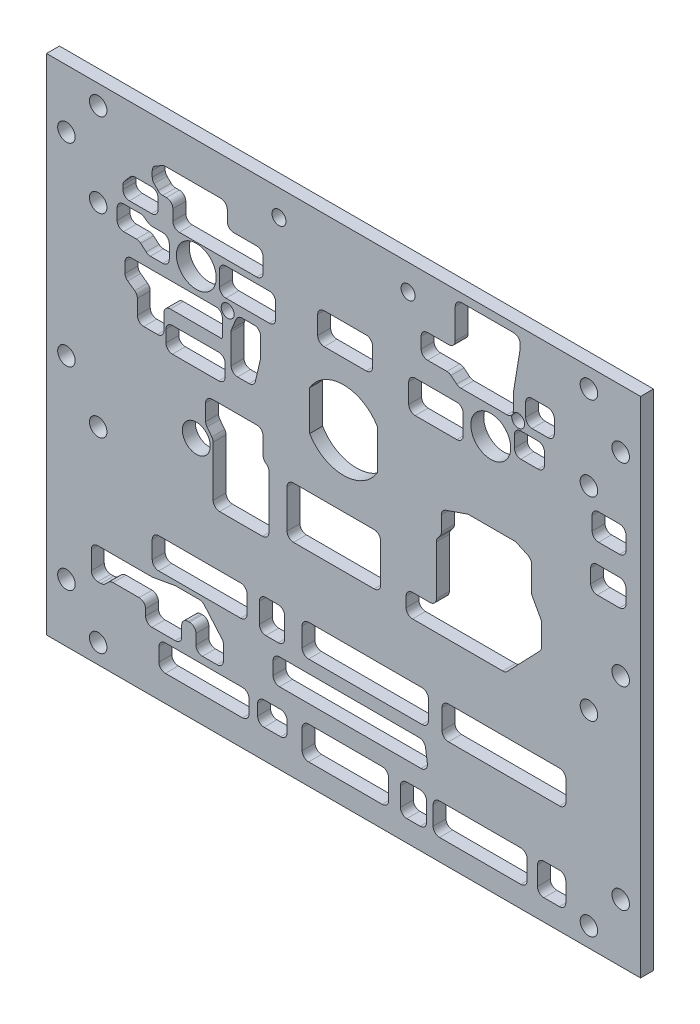
SolidWorks part; units mm, degrees
ref_plane "Front Plane" through (0, 0, 0) normal (0, 0, 1) x (1, 0, 0)
ref_plane "Top Plane" through (0, 0, 0) normal (0, 1, 0) x (1, 0, 0)
ref_plane "Right Plane" through (0, 0, 0) normal (1, 0, 0) x (0, 0, -1)
sketch "Sketch1" plane through (0, 0, 0) normal (0, 0, 1) x (1, 0, 0)
  line L8 (0, 123.825) -> (-146.05, 123.825)
  line L9 (-146.05, 123.825) -> (-146.05, 0)
  line L10 (-146.05, 0) -> (0, 0)
  line L11 (0, 0) -> (0, 123.825)
extrude "Boss-Extrude1" add sketch "Sketch1" against normal blind 3.175
hole_wizard "#6 Clearance Hole1" positions "Sketch3" profile "Sketch2" hole size "#6" standard "ANSI Inch" end condition through all
sketch "Sketch3" plane through (0, 0, -3.175) normal (0, 0, -1) x (-1, 0, 0)
  line L0 (88.9, 117.475) -> (57.15, 117.475) construction
  point P0 (12.7, 119.0625)
  point P9 (133.35, 119.0625)
  point P12 (141.1605, 109.5375)
  point P15 (133.35, 98.425)
  point P18 (141.1605, 61.9125)
  point P21 (133.35, 50.673)
  point P24 (133.35, 4.7625)
  point P27 (12.7, 4.7625)
  point P30 (12.7, 50.673)
  point P33 (12.7, 98.425)
  point P36 (4.8895, 109.5375)
  point P39 (141.1605, 14.2875)
  point P42 (4.8895, 14.2875)
  point P45 (4.8895, 61.9125)
sketch "Sketch2" plane through (-12.7, 119.0625, -3.175) normal (1, 0, 0) x (0, 1, 0)
  line L0 (0, 0) -> (0, 3.175)
  line L1 (0, 3.175) -> (2.1526, 3.175)
  line L2 (2.1526, 3.175) -> (2.1526, 0)
  line L5 (2.1526, 0) -> (0, 0)
  line L11 (0, -6.35) -> (0, 107.95) construction
  dimension "Thru Hole Dia." = 4.3053
  dimension "Thru Hole Depth" = 3.175
sketch "Sketch4" plane through (0, 0, -3.175) normal (0, 0, -1) x (-1, 0, 0)
  line L0 (109.22, 96.901) -> (89.8757, 96.901) construction
  line L1 (109.22, 96.901) -> (101.5141, 91.3023) construction
  line L2 (81.3435, 85.0323) -> (81.3435, 75.2417)
  line L3 (64.7065, 75.2417) -> (64.7065, 85.0323)
  line L5 (36.83, 96.901) -> (21.0814, 96.901) construction
  line L6 (36.83, 96.901) -> (30.0948, 103.6362) construction
  circle A0 centre (36.83, 96.901) radius 4.9022
  circle A1 centre (36.83, 60.325) radius 3.7703
  circle A2 centre (109.22, 60.325) radius 3.429
  circle A3 centre (109.22, 96.901) radius 4.9022
  circle A4 centre (36.83, 66.525) radius 1.125
  circle A5 centre (101.5141, 91.3023) radius 1.5875
  arc A6 (81.3435, 85.0323) -> (64.7065, 85.0323) centre (73.025, 80.137) ccw
  arc A7 (64.7065, 75.2417) -> (81.3435, 75.2417) centre (73.025, 80.137) ccw
  circle A8 centre (30.0948, 103.6362) radius 1.5875
  dimension "D1" = 7.5406
  dimension "D2" = 9.8044
  dimension "D3" = 6.858
  dimension "D4" = 2.25
  dimension "D5" = 3.175
  dimension "D7" = 9.8044
  dimension "D9" = 315
  dimension "D11" = 3.175
  dimension "D6" = 9.525
  dimension "D8" = 36
  dimension "D10" = 9.525
  dimension "D12" = 6.2
extrude "Switch Mount Holes" cut sketch "Sketch4" against normal through all
hole_wizard "#4 Clearance Hole1" positions "Sketch6" profile "Sketch5" hole size "#4" standard "ANSI Inch" end condition through all
sketch "Sketch6" plane through (0, 0, 0) normal (0, 0, 1) x (1, 0, 0)
  point P3 (-88.9, 117.475)
  point P6 (-57.15, 117.475)
sketch "Sketch5" plane through (-88.9, 117.475, 0) normal (1, 0, 0) x (0, -1, 0)
  line L0 (0, 0) -> (0, 3.175)
  line L1 (0, 3.175) -> (1.7272, 3.175)
  line L2 (1.7272, 3.175) -> (1.7272, 0)
  line L5 (1.7272, 0) -> (0, 0)
  line L11 (0, -6.35) -> (0, 107.95) construction
  dimension "Thru Hole Dia." = 3.4544
  dimension "Thru Hole Depth" = 3.175
sketch "Sketch7" plane through (0, 0, -3.175) normal (0, 0, -1) x (-1, 0, 0)
  line L0 (50.1883, 55.6576) -> (50.1883, 67.7772)
  line L9 (30.4526, 77.4046) -> (27.7399, 76.1861)
  line L10 (26.8029, 74.738) -> (26.8029, 68.7138)
  line L16 (48.9573, 70.478) -> (48.9573, 74.1496)
  line L17 (47.8891, 75.6498) -> (42.6693, 77.4567)
  line L18 (42.15, 77.544) -> (31.1031, 77.544)
  line L22 (24.3417, 58.3195) -> (24.3417, 63.425)
  line L24 (5.1812, 94.0944) -> (10.326, 94.0944)
  line L25 (3.5937, 92.5069) -> (3.5937, 89.2086)
  line L26 (5.1812, 87.6211) -> (10.326, 87.6211)
  line L27 (11.9135, 92.5069) -> (11.9135, 89.2086)
  line L28 (5.1812, 82.7314) -> (10.6748, 82.7314)
  line L29 (3.5937, 81.1439) -> (3.5937, 77.808)
  line L30 (5.1812, 76.2205) -> (10.6748, 76.2205)
  line L31 (12.2623, 81.1439) -> (12.2623, 77.808)
  line L36 (65.5088, 62.7223) -> (85.3289, 62.7223)
  line L37 (63.9213, 61.1348) -> (63.9213, 51.6801)
  line L38 (65.5088, 50.0926) -> (85.3289, 50.0926)
  line L39 (86.9164, 61.1348) -> (86.9164, 51.6801)
  line L40 (45.5644, 120.203) -> (45.5644, 112.8447)
  line L41 (47.1519, 111.2572) -> (52.3642, 111.2572)
  line L42 (53.9517, 109.6697) -> (53.9517, 106.9355)
  line L43 (52.3642, 105.348) -> (47.5969, 105.348)
  line L44 (46.598, 104.9944) -> (45.1842, 103.8499)
  line L45 (44.1854, 103.4962) -> (32.8826, 103.4962)
  line L49 (22.7874, 110.0698) -> (26.67, 110.0698)
  line L50 (28.2575, 108.4823) -> (28.2575, 105.2469)
  line L51 (26.67, 103.6594) -> (22.7874, 103.6594)
  line L52 (21.1999, 105.2469) -> (21.1999, 108.4823)
  line L53 (31.0254, 97.333) -> (31.0254, 100.1621)
  line L54 (29.4379, 101.7496) -> (25.2171, 101.7496)
  line L55 (23.6296, 100.1621) -> (23.6296, 97.333)
  line L56 (25.2171, 95.7455) -> (29.4379, 95.7455)
  line L57 (45.1936, 100.0129) -> (55.4124, 100.0129)
  line L58 (56.9999, 98.4254) -> (56.9999, 93.6299)
  line L59 (55.4124, 92.0424) -> (45.1936, 92.0424)
  line L60 (43.6061, 93.6299) -> (43.6061, 98.4254)
  line L61 (67.4661, 103.1819) -> (77.7971, 103.1819)
  line L62 (79.3846, 101.5944) -> (79.3846, 97.1115)
  line L63 (77.7971, 95.524) -> (67.4661, 95.524)
  line L64 (65.8786, 97.1115) -> (65.8786, 101.5944)
  line L65 (101.6113, 112.8205) -> (101.6113, 110.2692)
  line L66 (100.0238, 108.6817) -> (94.374, 108.6817)
  line L67 (92.7865, 107.0942) -> (92.7865, 103.6594)
  line L68 (94.374, 102.0719) -> (113.3987, 102.0719)
  line L69 (114.9862, 103.6594) -> (114.9862, 106.2952)
  line L70 (116.5737, 107.8827) -> (117.4821, 107.8827)
  line L71 (118.6047, 108.3477) -> (119.594, 109.337)
  line L72 (120.059, 110.4596) -> (120.059, 111.8874)
  line L73 (119.235, 113.2792) -> (117.5341, 114.2123)
  line L74 (116.7706, 114.408) -> (103.1988, 114.408)
  line L75 (118.6106, 106.776) -> (118.6106, 104.2323)
  line L76 (120.1981, 102.6448) -> (125.6772, 102.6448)
  line L77 (127.2647, 104.2323) -> (127.2647, 105.1854)
  line L78 (126.8771, 106.2249) -> (125.4846, 107.8322)
  line L79 (124.2782, 108.3802) -> (120.1916, 108.3635)
  line L80 (128.6873, 99.6767) -> (128.6873, 96.9557)
  line L81 (127.0998, 95.3682) -> (123.9282, 95.3682)
  line L82 (122.8887, 94.9806) -> (121.5452, 93.8167)
  line L83 (120.5057, 93.429) -> (117.4622, 93.429)
  line L84 (115.8747, 95.0165) -> (115.8747, 98.3811)
  line L85 (117.4622, 99.9686) -> (120.0973, 99.9686)
  line L86 (120.9827, 100.2384) -> (122.1076, 100.9943)
  line L87 (122.993, 101.2642) -> (127.0998, 101.2642)
  line L88 (91.2932, 100.6292) -> (101.9492, 100.6292)
  line L89 (103.5367, 99.0417) -> (103.5367, 95.3671)
  line L90 (101.9492, 93.7796) -> (91.2932, 93.7796)
  line L91 (89.7057, 95.3671) -> (89.7057, 99.0417)
  line L92 (93.3875, 89.9303) -> (93.3875, 85.5072)
  line L93 (93.4289, 85.1472) -> (94.7051, 79.6669)
  line L94 (96.2512, 78.4394) -> (99.0869, 78.4394)
  line L95 (100.6744, 80.0269) -> (100.6744, 87.2579)
  line L96 (100.552, 87.8693) -> (99.4367, 90.5417)
  line L97 (97.9716, 91.5178) -> (94.975, 91.5178)
  line L98 (116.6884, 76.8675) -> (116.6884, 79.8001)
  line L99 (115.1009, 81.3876) -> (103.7165, 81.3876)
  line L100 (102.129, 79.8001) -> (102.129, 76.8675)
  line L101 (103.7165, 75.28) -> (115.1009, 75.28)
  line L102 (118.7649, 77.6401) -> (122.1358, 77.6401)
  line L107 (125.1538, 90.7081) -> (104.3937, 90.7081)
  line L108 (102.8062, 89.1206) -> (102.8062, 85.2592)
  line L110 (92.7865, 68.98) -> (92.7865, 64.8285)
  line L111 (92.0912, 63.5154) -> (92.0685, 63.5)
  line L112 (91.3732, 62.1869) -> (91.3732, 49.1513)
  line L113 (92.9607, 47.5638) -> (103.499, 47.5638)
  line L114 (105.0865, 49.1513) -> (105.0865, 61.5326)
  line L115 (105.4181, 62.5037) -> (106.6032, 64.0363)
  line L116 (106.9348, 65.0074) -> (106.9348, 68.98)
  line L117 (105.3473, 70.5675) -> (94.374, 70.5675)
  line L118 (19.9317, 34.7214) -> (47.2287, 34.7214)
  line L119 (48.8162, 33.1339) -> (48.8162, 28.2593)
  line L120 (47.2287, 26.6718) -> (19.9317, 26.6718)
  line L121 (18.3442, 28.2593) -> (18.3442, 33.1339)
  line L122 (52.1537, 33.3607) -> (52.1537, 28.7019)
  line L123 (53.7412, 27.1144) -> (81.6222, 27.1144)
  line L124 (83.2097, 28.7019) -> (83.2097, 33.3607)
  line L125 (81.6222, 34.9482) -> (53.7412, 34.9482)
  line L126 (89.0857, 34.9482) -> (92.1336, 34.9482)
  line L127 (93.7211, 33.3607) -> (93.7211, 28.4272)
  line L128 (92.1336, 26.8397) -> (89.0857, 26.8397)
  line L129 (87.4982, 28.4272) -> (87.4982, 33.3607)
  line L130 (98.3248, 34.9482) -> (118.4715, 34.9482)
  line L131 (120.059, 33.3607) -> (120.059, 29.0335)
  line L132 (96.7373, 33.3607) -> (96.7373, 29.0335)
  line L133 (98.3248, 27.446) -> (118.4715, 27.446)
  line L137 (130.8099, 18.8799) -> (131.5742, 18.1156)
  line L138 (132.6968, 17.6506) -> (133.4449, 17.6506)
  line L139 (135.0324, 19.2381) -> (135.0324, 23.7437)
  line L141 (120.198, 25.3312) -> (133.4449, 25.3312)
  line L142 (107.2606, 25.7828) -> (102.9308, 20.7547)
  line L143 (102.5462, 19.7188) -> (102.5462, 16.2301)
  line L144 (104.1337, 14.6426) -> (107.7174, 14.6426)
  line L145 (109.3049, 16.2301) -> (109.3049, 18.7206)
  line L146 (110.8924, 20.3081) -> (111.2259, 20.3081)
  line L147 (112.8134, 18.7206) -> (112.8134, 16.2076)
  line L148 (114.4009, 14.6201) -> (120.1137, 14.6201)
  line L149 (108.4635, 26.3345) -> (114.2367, 26.3345)
  line L150 (114.5127, 26.3103) -> (119.9221, 25.3554)
  line L151 (129.6874, 19.3449) -> (123.2887, 19.3449)
  line L152 (121.7012, 17.7574) -> (121.7012, 16.2076)
  line L153 (54.4377, 23.9876) -> (88.7667, 23.9876)
  line L154 (90.3542, 22.4001) -> (90.3542, 19.2172)
  line L155 (88.7667, 17.6297) -> (53.9837, 17.6297)
  line L156 (52.4121, 19.4414) -> (52.8661, 22.6242)
  line L157 (19.972, 12.9834) -> (23.773, 12.9834)
  line L158 (25.3605, 11.3959) -> (25.3605, 6.8041)
  line L159 (23.773, 5.2166) -> (19.972, 5.2166)
  line L160 (18.3845, 6.8041) -> (18.3845, 11.3959)
  line L161 (29.4607, 12.9834) -> (49.418, 12.9834)
  line L162 (51.0055, 11.3959) -> (51.0055, 6.8041)
  line L163 (49.418, 5.2166) -> (29.4607, 5.2166)
  line L164 (27.8732, 6.8041) -> (27.8732, 11.3959)
  line L165 (54.1946, 12.9834) -> (57.4655, 12.9834)
  line L166 (59.053, 11.3959) -> (59.053, 6.8041)
  line L167 (57.4655, 5.2166) -> (54.1946, 5.2166)
  line L168 (52.6071, 6.8041) -> (52.6071, 11.3959)
  line L169 (63.5238, 13.2586) -> (81.6126, 13.2586)
  line L170 (83.2001, 11.6711) -> (83.2001, 6.8041)
  line L171 (81.6126, 5.2166) -> (63.5238, 5.2166)
  line L172 (61.9363, 6.8041) -> (61.9363, 11.6711)
  line L173 (26.6062, 67.9484) -> (24.5383, 64.1904)
  line L174 (88.4887, 12.9381) -> (92.5645, 12.9381)
  line L175 (86.9012, 11.3506) -> (86.9012, 8.7068)
  line L176 (88.4887, 7.1193) -> (92.5645, 7.1193)
  line L177 (94.152, 11.3506) -> (94.152, 8.7068)
  line L178 (97.8585, 12.9381) -> (116.8363, 12.9381)
  line L179 (96.271, 11.3506) -> (96.271, 8.0414)
  line L180 (97.8585, 6.4539) -> (116.8363, 6.4539)
  line L181 (118.4238, 11.3506) -> (118.4238, 8.0414)
  line L182 (24.7832, 57.2209) -> (32.747, 48.9138)
  line L183 (51.7758, 54.0701) -> (56.0639, 54.0701)
  line L184 (57.6514, 52.4826) -> (57.6514, 50.0124)
  line L185 (33.8929, 48.4249) -> (56.0639, 48.4249)
  line L186 (49.2742, 69.5263) -> (49.8715, 68.7289)
  line L189 (31.2951, 108.7766) -> (31.2951, 105.0837)
  line L190 (43.9769, 121.7905) -> (31.1878, 121.7905)
  line L191 (29.6003, 120.203) -> (29.6003, 119.2785)
  line L192 (29.6216, 119.0193) -> (31.2738, 109.0357)
  line L194 (123.7233, 82.8593) -> (123.7233, 79.2276)
  line L195 (117.1774, 79.2276) -> (117.1774, 83.0623)
  line L196 (115.5899, 84.6498) -> (102.9278, 84.6498)
  line L197 (124.3822, 84.1469) -> (126.0824, 85.3731)
  line L198 (126.7413, 86.6607) -> (126.7413, 89.1206)
  arc A2 (116.8363, 12.9381) -> (118.4238, 11.3506) centre (116.8363, 11.3506) cw
  arc A3 (96.271, 8.0414) -> (97.8585, 6.4539) centre (97.8585, 8.0414) ccw
  arc A4 (116.8363, 6.4539) -> (118.4238, 8.0414) centre (116.8363, 8.0414) ccw
  arc A5 (97.8585, 12.9381) -> (96.271, 11.3506) centre (97.8585, 11.3506) ccw
  arc A6 (92.5645, 12.9381) -> (94.152, 11.3506) centre (92.5645, 11.3506) cw
  arc A7 (86.9012, 8.7068) -> (88.4887, 7.1193) centre (88.4887, 8.7068) ccw
  arc A8 (92.5645, 7.1193) -> (94.152, 8.7068) centre (92.5645, 8.7068) ccw
  arc A9 (63.5238, 5.2166) -> (61.9363, 6.8041) centre (63.5238, 6.8041) cw
  arc A10 (88.4887, 12.9381) -> (86.9012, 11.3506) centre (88.4887, 11.3506) ccw
  arc A11 (83.2001, 6.8041) -> (81.6126, 5.2166) centre (81.6126, 6.8041) cw
  arc A12 (81.6126, 13.2586) -> (83.2001, 11.6711) centre (81.6126, 11.6711) cw
  arc A13 (54.1946, 5.2166) -> (52.6071, 6.8041) centre (54.1946, 6.8041) cw
  arc A14 (63.5238, 13.2586) -> (61.9363, 11.6711) centre (63.5238, 11.6711) ccw
  arc A15 (59.053, 6.8041) -> (57.4655, 5.2166) centre (57.4655, 6.8041) cw
  arc A16 (57.4655, 12.9834) -> (59.053, 11.3959) centre (57.4655, 11.3959) cw
  arc A17 (54.1946, 12.9834) -> (52.6071, 11.3959) centre (54.1946, 11.3959) ccw
  arc A18 (51.0055, 6.8041) -> (49.418, 5.2166) centre (49.418, 6.8041) cw
  arc A19 (29.4607, 5.2166) -> (27.8732, 6.8041) centre (29.4607, 6.8041) cw
  arc A20 (49.418, 12.9834) -> (51.0055, 11.3959) centre (49.418, 11.3959) cw
  arc A21 (29.4607, 12.9834) -> (27.8732, 11.3959) centre (29.4607, 11.3959) ccw
  arc A22 (19.972, 5.2166) -> (18.3845, 6.8041) centre (19.972, 6.8041) cw
  arc A23 (25.3605, 6.8041) -> (23.773, 5.2166) centre (23.773, 6.8041) cw
  arc A24 (23.773, 12.9834) -> (25.3605, 11.3959) centre (23.773, 11.3959) cw
  arc A25 (19.972, 12.9834) -> (18.3845, 11.3959) centre (19.972, 11.3959) ccw
  arc A26 (90.3542, 19.2172) -> (88.7667, 17.6297) centre (88.7667, 19.2172) cw
  arc A27 (53.9837, 17.6297) -> (52.4121, 19.4414) centre (53.9837, 19.2172) cw
  arc A28 (88.7667, 23.9876) -> (90.3542, 22.4001) centre (88.7667, 22.4001) cw
  arc A29 (123.2887, 19.3449) -> (121.7012, 17.7574) centre (123.2887, 17.7574) ccw
  arc A30 (120.1137, 14.6201) -> (121.7012, 16.2076) centre (120.1137, 16.2076) ccw
  arc A31 (112.8134, 16.2076) -> (114.4009, 14.6201) centre (114.4009, 16.2076) ccw
  arc A32 (114.2367, 26.3345) -> (114.5127, 26.3103) centre (114.2367, 24.747) cw
  arc A33 (109.3049, 18.7206) -> (110.8924, 20.3081) centre (110.8924, 18.7206) cw
  arc A34 (107.7174, 14.6426) -> (109.3049, 16.2301) centre (107.7174, 16.2301) ccw
  arc A35 (102.5462, 16.2301) -> (104.1337, 14.6426) centre (104.1337, 16.2301) ccw
  arc A36 (111.2259, 20.3081) -> (112.8134, 18.7206) centre (111.2259, 18.7206) cw
  arc A37 (102.9308, 20.7547) -> (102.5462, 19.7188) centre (104.1337, 19.7188) ccw
  arc A38 (133.4449, 17.6506) -> (135.0324, 19.2381) centre (133.4449, 19.2381) ccw
  arc A39 (131.5742, 18.1156) -> (132.6968, 17.6506) centre (132.6968, 19.2381) ccw
  arc A40 (129.6874, 19.3449) -> (130.8099, 18.8799) centre (129.6874, 17.7574) cw
  arc A41 (54.4377, 23.9876) -> (52.8661, 22.6242) centre (54.4377, 22.4001) ccw
  arc A42 (135.0324, 23.7437) -> (133.4449, 25.3312) centre (133.4449, 23.7437) ccw
  arc A43 (120.198, 25.3312) -> (119.9221, 25.3554) centre (120.198, 26.9187) cw
  arc A44 (96.7373, 29.0335) -> (98.3248, 27.446) centre (98.3248, 29.0335) ccw
  arc A45 (120.059, 29.0335) -> (118.4715, 27.446) centre (118.4715, 29.0335) cw
  arc A46 (107.2606, 25.7828) -> (108.4635, 26.3345) centre (108.4635, 24.747) cw
  arc A47 (118.4715, 34.9482) -> (120.059, 33.3607) centre (118.4715, 33.3607) cw
  arc A48 (98.3248, 34.9482) -> (96.7373, 33.3607) centre (98.3248, 33.3607) ccw
  arc A49 (89.0857, 26.8397) -> (87.4982, 28.4272) centre (89.0857, 28.4272) cw
  arc A50 (93.7211, 28.4272) -> (92.1336, 26.8397) centre (92.1336, 28.4272) cw
  arc A51 (92.1336, 34.9482) -> (93.7211, 33.3607) centre (92.1336, 33.3607) cw
  arc A52 (83.2097, 33.3607) -> (81.6222, 34.9482) centre (81.6222, 33.3607) ccw
  arc A53 (81.6222, 27.1144) -> (83.2097, 28.7019) centre (81.6222, 28.7019) ccw
  arc A54 (89.0857, 34.9482) -> (87.4982, 33.3607) centre (89.0857, 33.3607) ccw
  arc A55 (52.1537, 28.7019) -> (53.7412, 27.1144) centre (53.7412, 28.7019) ccw
  arc A56 (19.9317, 26.6718) -> (18.3442, 28.2593) centre (19.9317, 28.2593) cw
  arc A57 (48.8162, 28.2593) -> (47.2287, 26.6718) centre (47.2287, 28.2593) cw
  arc A58 (52.1537, 33.3607) -> (53.7412, 34.9482) centre (53.7412, 33.3607) cw
  arc A59 (47.2287, 34.7214) -> (48.8162, 33.1339) centre (47.2287, 33.1339) cw
  arc A60 (106.9348, 68.98) -> (105.3473, 70.5675) centre (105.3473, 68.98) ccw
  arc A61 (19.9317, 34.7214) -> (18.3442, 33.1339) centre (19.9317, 33.1339) ccw
  arc A62 (105.0865, 61.5326) -> (105.4181, 62.5037) centre (106.674, 61.5326) cw
  arc A63 (103.499, 47.5638) -> (105.0865, 49.1513) centre (103.499, 49.1513) ccw
  arc A64 (91.3732, 49.1513) -> (92.9607, 47.5638) centre (92.9607, 49.1513) ccw
  arc A65 (92.0685, 63.5) -> (91.3732, 62.1869) centre (92.9607, 62.1869) ccw
  arc A66 (106.6032, 64.0363) -> (106.9348, 65.0074) centre (105.3473, 65.0074) ccw
  arc A67 (92.7865, 64.8285) -> (92.0912, 63.5154) centre (91.199, 64.8285) cw
  arc A68 (102.8062, 85.2592) -> (102.9278, 84.6498) centre (104.3937, 85.2592) ccw
  arc A69 (92.7865, 68.98) -> (94.374, 70.5675) centre (94.374, 68.98) cw
  arc A70 (104.3937, 90.7081) -> (102.8062, 89.1206) centre (104.3937, 89.1206) ccw
  arc A71 (126.7413, 89.1206) -> (125.1538, 90.7081) centre (125.1538, 89.1206) ccw
  arc A75 (122.1358, 77.6401) -> (123.7233, 79.2276) centre (122.1358, 79.2276) ccw
  arc A76 (102.129, 76.8675) -> (103.7165, 75.28) centre (103.7165, 76.8675) ccw
  arc A77 (103.7165, 81.3876) -> (102.129, 79.8001) centre (103.7165, 79.8001) ccw
  arc A78 (118.7649, 77.6401) -> (117.1774, 79.2276) centre (118.7649, 79.2276) cw
  arc A79 (116.6884, 79.8001) -> (115.1009, 81.3876) centre (115.1009, 79.8001) ccw
  arc A80 (116.6884, 76.8675) -> (115.1009, 75.28) centre (115.1009, 76.8675) cw
  arc A81 (100.6744, 87.2579) -> (100.552, 87.8693) centre (99.0869, 87.2579) ccw
  arc A82 (99.0869, 78.4394) -> (100.6744, 80.0269) centre (99.0869, 80.0269) ccw
  arc A83 (99.4367, 90.5417) -> (97.9716, 91.5178) centre (97.9716, 89.9303) ccw
  arc A84 (94.7051, 79.6669) -> (96.2512, 78.4394) centre (96.2512, 80.0269) ccw
  arc A85 (93.3875, 85.5072) -> (93.4289, 85.1472) centre (94.975, 85.5072) ccw
  arc A86 (93.3875, 89.9303) -> (94.975, 91.5178) centre (94.975, 89.9303) cw
  arc A87 (91.2932, 93.7796) -> (89.7057, 95.3671) centre (91.2932, 95.3671) cw
  arc A88 (103.5367, 95.3671) -> (101.9492, 93.7796) centre (101.9492, 95.3671) cw
  arc A89 (101.9492, 100.6292) -> (103.5367, 99.0417) centre (101.9492, 99.0417) cw
  arc A90 (122.1076, 100.9943) -> (122.993, 101.2642) centre (122.993, 99.6767) cw
  arc A91 (120.0973, 99.9686) -> (120.9827, 100.2384) centre (120.0973, 101.5561) ccw
  arc A92 (115.8747, 98.3811) -> (117.4622, 99.9686) centre (117.4622, 98.3811) cw
  arc A93 (117.4622, 93.429) -> (115.8747, 95.0165) centre (117.4622, 95.0165) cw
  arc A94 (121.5452, 93.8167) -> (120.5057, 93.429) centre (120.5057, 95.0165) cw
  arc A95 (91.2932, 100.6292) -> (89.7057, 99.0417) centre (91.2932, 99.0417) ccw
  arc A96 (123.9282, 95.3682) -> (122.8887, 94.9806) centre (123.9282, 93.7807) ccw
  arc A97 (128.6873, 96.9557) -> (127.0998, 95.3682) centre (127.0998, 96.9557) cw
  arc A98 (128.6873, 99.6767) -> (127.0998, 101.2642) centre (127.0998, 99.6767) ccw
  arc A99 (125.4846, 107.8322) -> (124.2782, 108.3802) centre (124.2847, 106.7928) ccw
  arc A100 (125.6772, 102.6448) -> (127.2647, 104.2323) centre (125.6772, 104.2323) ccw
  arc A101 (127.2647, 105.1854) -> (126.8771, 106.2249) centre (125.6772, 105.1854) ccw
  arc A102 (118.6106, 104.2323) -> (120.1981, 102.6448) centre (120.1981, 104.2323) ccw
  arc A103 (117.5341, 114.2123) -> (116.7706, 114.408) centre (116.7706, 112.8205) ccw
  arc A104 (120.059, 111.8874) -> (119.235, 113.2792) centre (118.4715, 111.8874) ccw
  arc A105 (119.594, 109.337) -> (120.059, 110.4596) centre (118.4715, 110.4596) ccw
  arc A106 (117.4821, 107.8827) -> (118.6047, 108.3477) centre (117.4821, 109.4702) ccw
  arc A107 (114.9862, 106.2952) -> (116.5737, 107.8827) centre (116.5737, 106.2952) cw
  arc A108 (113.3987, 102.0719) -> (114.9862, 103.6594) centre (113.3987, 103.6594) ccw
  arc A109 (92.7865, 103.6594) -> (94.374, 102.0719) centre (94.374, 103.6594) ccw
  arc A110 (94.374, 108.6817) -> (92.7865, 107.0942) centre (94.374, 107.0942) ccw
  arc A111 (101.6113, 110.2692) -> (100.0238, 108.6817) centre (100.0238, 110.2692) cw
  arc A112 (101.6113, 112.8205) -> (103.1988, 114.408) centre (103.1988, 112.8205) cw
  arc A113 (118.6106, 106.776) -> (120.1916, 108.3635) centre (120.1981, 106.776) cw
  arc A114 (79.3846, 97.1115) -> (77.7971, 95.524) centre (77.7971, 97.1115) cw
  arc A115 (67.4661, 95.524) -> (65.8786, 97.1115) centre (67.4661, 97.1115) cw
  arc A116 (77.7971, 103.1819) -> (79.3846, 101.5944) centre (77.7971, 101.5944) cw
  arc A117 (67.4661, 103.1819) -> (65.8786, 101.5944) centre (67.4661, 101.5944) ccw
  arc A118 (56.9999, 93.6299) -> (55.4124, 92.0424) centre (55.4124, 93.6299) cw
  arc A119 (45.1936, 92.0424) -> (43.6061, 93.6299) centre (45.1936, 93.6299) cw
  arc A120 (55.4124, 100.0129) -> (56.9999, 98.4254) centre (55.4124, 98.4254) cw
  arc A121 (45.1936, 100.0129) -> (43.6061, 98.4254) centre (45.1936, 98.4254) ccw
  arc A122 (23.6296, 97.333) -> (25.2171, 95.7455) centre (25.2171, 97.333) ccw
  arc A123 (25.2171, 101.7496) -> (23.6296, 100.1621) centre (25.2171, 100.1621) ccw
  arc A124 (31.0254, 100.1621) -> (29.4379, 101.7496) centre (29.4379, 100.1621) ccw
  arc A125 (22.7874, 103.6594) -> (21.1999, 105.2469) centre (22.7874, 105.2469) cw
  arc A126 (28.2575, 105.2469) -> (26.67, 103.6594) centre (26.67, 105.2469) cw
  arc A127 (31.0254, 97.333) -> (29.4379, 95.7455) centre (29.4379, 97.333) cw
  arc A128 (26.67, 110.0698) -> (28.2575, 108.4823) centre (26.67, 108.4823) cw
  arc A129 (22.7874, 110.0698) -> (21.1999, 108.4823) centre (22.7874, 108.4823) ccw
  arc A130 (32.8826, 103.4962) -> (31.2951, 105.0837) centre (32.8826, 105.0837) cw
  arc A131 (47.5969, 105.348) -> (46.598, 104.9944) centre (47.5969, 103.7605) ccw
  arc A132 (45.1842, 103.8499) -> (44.1854, 103.4962) centre (44.1854, 105.0837) cw
  arc A133 (52.3642, 111.2572) -> (53.9517, 109.6697) centre (52.3642, 109.6697) cw
  arc A134 (45.5644, 112.8447) -> (47.1519, 111.2572) centre (47.1519, 112.8447) ccw
  arc A135 (53.9517, 106.9355) -> (52.3642, 105.348) centre (52.3642, 106.9355) cw
  arc A136 (43.9769, 121.7905) -> (45.5644, 120.203) centre (43.9769, 120.203) cw
  arc A138 (85.3289, 62.7223) -> (86.9164, 61.1348) centre (85.3289, 61.1348) cw
  arc A139 (63.9213, 51.6801) -> (65.5088, 50.0926) centre (65.5088, 51.6801) ccw
  arc A140 (85.3289, 50.0926) -> (86.9164, 51.6801) centre (85.3289, 51.6801) ccw
  arc A141 (65.5088, 62.7223) -> (63.9213, 61.1348) centre (65.5088, 61.1348) ccw
  arc A142 (10.6748, 82.7314) -> (12.2623, 81.1439) centre (10.6748, 81.1439) cw
  arc A143 (3.5937, 77.808) -> (5.1812, 76.2205) centre (5.1812, 77.808) ccw
  arc A144 (10.6748, 76.2205) -> (12.2623, 77.808) centre (10.6748, 77.808) ccw
  arc A145 (5.1812, 82.7314) -> (3.5937, 81.1439) centre (5.1812, 81.1439) ccw
  arc A146 (10.326, 94.0944) -> (11.9135, 92.5069) centre (10.326, 92.5069) cw
  arc A147 (3.5937, 89.2086) -> (5.1812, 87.6211) centre (5.1812, 89.2086) ccw
  arc A148 (10.326, 87.6211) -> (11.9135, 89.2086) centre (10.326, 89.2086) ccw
  arc A149 (24.7832, 57.2209) -> (24.3417, 58.3195) centre (25.9292, 58.3195) cw
  arc A150 (5.1812, 94.0944) -> (3.5937, 92.5069) centre (5.1812, 92.5069) ccw
  arc A151 (42.6693, 77.4567) -> (42.15, 77.544) centre (42.15, 75.9565) ccw
  arc A152 (48.9573, 74.1496) -> (47.8891, 75.6498) centre (47.3698, 74.1496) ccw
  arc A153 (49.2742, 69.5263) -> (48.9573, 70.478) centre (50.5448, 70.478) cw
  arc A154 (26.8029, 68.7138) -> (26.6062, 67.9484) centre (25.2154, 68.7138) cw
  arc A155 (24.5383, 64.1904) -> (24.3417, 63.425) centre (25.9292, 63.425) ccw
  arc A156 (27.7399, 76.1861) -> (26.8029, 74.738) centre (28.3904, 74.738) ccw
  arc A157 (30.4526, 77.4046) -> (31.1031, 77.544) centre (31.1031, 75.9565) cw
  arc A158 (50.1883, 67.7772) -> (49.8715, 68.7289) centre (48.6008, 67.7772) ccw
  arc A159 (50.1883, 55.6576) -> (51.7758, 54.0701) centre (51.7758, 55.6576) ccw
  arc A160 (57.6514, 50.0124) -> (56.0639, 48.4249) centre (56.0639, 50.0124) cw
  arc A161 (56.0639, 54.0701) -> (57.6514, 52.4826) centre (56.0639, 52.4826) cw
  arc A162 (32.747, 48.9138) -> (33.8929, 48.4249) centre (33.8929, 50.0124) ccw
  arc A164 (31.2951, 108.7766) -> (31.2738, 109.0357) centre (29.7076, 108.7766) ccw
  arc A165 (29.6003, 119.2785) -> (29.6216, 119.0193) centre (31.1878, 119.2785) ccw
  arc A166 (31.1878, 121.7905) -> (29.6003, 120.203) centre (31.1878, 120.203) ccw
  arc A167 (117.1774, 83.0623) -> (115.5899, 84.6498) centre (115.5899, 83.0623) ccw
  arc A169 (123.7233, 82.8593) -> (124.3822, 84.1469) centre (125.3108, 82.8593) cw
  arc A170 (126.0824, 85.3731) -> (126.7413, 86.6607) centre (125.1538, 86.6607) ccw
  point P192 (59.053, 5.2166)
  point P199 (51.0055, 5.2166)
  point P204 (51.0055, 12.9834)
  point P211 (25.3605, 5.2166)
  point P214 (25.3605, 12.9834)
  point P269 (93.7211, 34.9482)
  point P272 (83.2097, 34.9482)
  point P367 (125.0073, 108.3832)
  point P388 (92.7865, 102.0719)
  dimension "D1" = 1.5875
  dimension "D2" = 1.5875
  dimension "D3" = 1.5875
  dimension "D4" = 1.5875
  dimension "D5" = 1.5875
extrude "Cut-Extrude1" cut sketch "Sketch7" against normal through all and the other way through all
